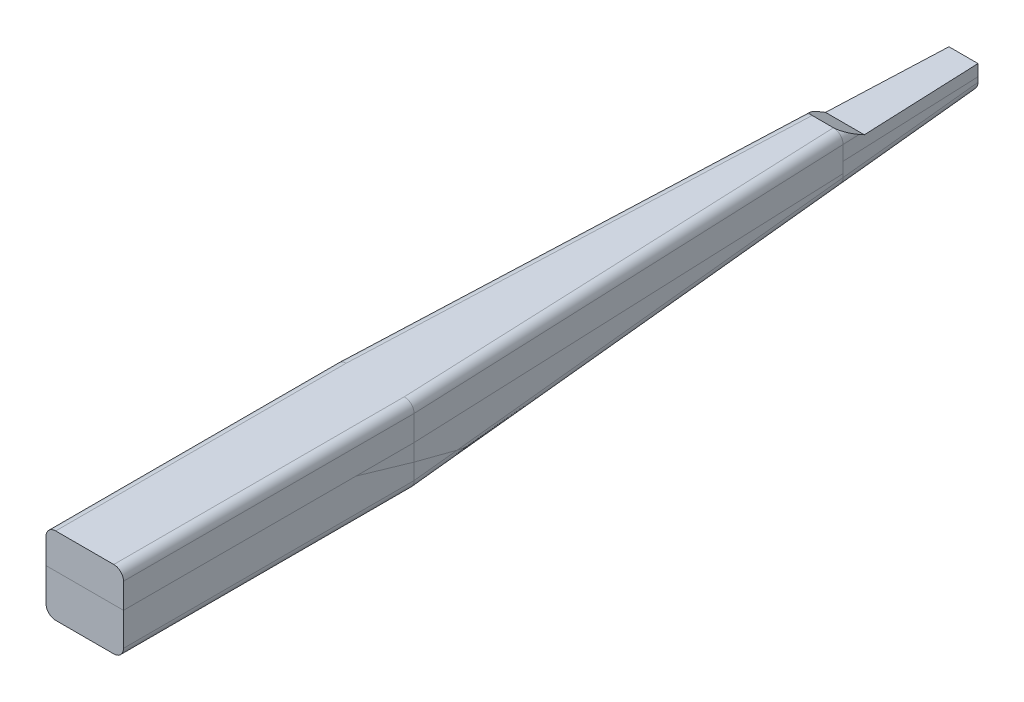
SolidWorks part; units mm, degrees
ref_plane "Front Plane" through (0, 0, 0) normal (0, 0, 1) x (1, 0, 0)
ref_plane "Top Plane" through (0, 0, 0) normal (0, 1, 0) x (1, 0, 0)
ref_plane "Right Plane" through (0, 0, 0) normal (1, 0, 0) x (0, 0, -1)
sketch "Sketch1" plane through (0, 0, 0) normal (0, 0, 1) x (1, 0, 0)
  line L1 (50.8, -50.8) -> (-50.8, -50.8)
  line L2 (50.8, -50.8) -> (50.8, 50.8)
  line L3 (50.8, 50.8) -> (-50.8, 50.8)
  line L4 (-50.8, -50.8) -> (-50.8, 50.8)
  line L5 (50.8, -50.8) -> (-50.8, 50.8) construction
  line L6 (50.8, 50.8) -> (-50.8, -50.8) construction
  point P0 (0, 0)
  dimension "D1" = 101.6
extrude "Boss-Extrude1" add sketch "Sketch1" against normal blind 381.1016
ref_plane "Plane1" through (0, 0, -1152.2456) normal (0, 0, -1) x (-1, 0, 0)
sketch "Sketch2" plane through (0, 0, -1152.2456) normal (0, 0, -1) x (-1, 0, 0)
  line L0 (0, 0) -> (0, 82.164) construction
  line L1 (-50.8, 50.8) -> (50.8, 50.8) construction
  line L2 (-19.05, 50.8) -> (19.05, 50.8)
  line L3 (-19.05, 50.8) -> (-19.05, 0)
  line L4 (-19.05, 0) -> (19.05, 0)
  line L5 (19.05, 50.8) -> (19.05, 0)
  line L6 (-19.05, 50.8) -> (19.05, 0) construction
  line L7 (-19.05, 0) -> (19.05, 50.8) construction
  point P3 (0, 25.4)
  dimension "D1" = 50.8
  dimension "D2" = 38.1
loft "Loft1" add profiles "Sketch2" section "Sketch2" section face at (0, 0, -381.1016) connector at (19.05, 50.8, -1152.2456) connector at (50.8, 50.8, -381.1016)
fillet "Fillet1" radius 12.7 8 edges at (-50.8, -50.8, -190.5508) (-50.8, 50.8, -190.5508) (50.8, 50.8, -190.5508) (50.8, -50.8, -190.5508)
sketch "Sketch3" plane through (50.8, 0, 0) normal (1, 0, 0) x (0, 0, -1)
  line L5 (0, -50.8) -> (0, 5.08)
  line L6 (0, -38.1) -> (0, 38.1) construction
  line L7 (0, 5.08) -> (304.8, 5.08)
  line L8 (304.8, 5.08) -> (475.411, -44.5873)
  line L9 (1152.2456, 0) -> (381.1016, -50.8) construction
  line L10 (475.411, -44.5873) -> (381.1016, -50.8)
  line L11 (381.1016, -50.8) -> (0, -50.8)
  dimension "D1" = 55.88
  dimension "D2" = 304.8
  dimension "D3" = 20
sketch "Sketch4" plane through (0, 0, 0) normal (1, 0, 0) x (0, 0, -1)
  line L0 (1152.2456, 50.8) -> (1152.2456, 34.036)
  line L1 (1152.2456, 38.1) -> (1152.2456, 12.6931) construction
  line L2 (1152.2456, 34.036) -> (996.7976, 34.036)
  line L3 (996.7976, 34.036) -> (967.7615, 50.8)
  line L4 (1152.2456, 50.8) -> (381.1016, 50.8) construction
  line L5 (967.7615, 50.8) -> (1152.2456, 50.8)
  dimension "D1" = 16.764
  dimension "D2" = 155.448
  dimension "D3" = 30
extrude "Cut-Extrude2" cut sketch "Sketch4" against normal mid plane 355.7016
split "Split1" trim tools "Sketch3" bodies to split 104 resulting bodies 105 106
ref_plane "Plane2" through (0, 5.08, 0) normal (0, 1, 0) x (1, 0, 0)
ref_plane "Plane3" through (0, 0, -967.7615) normal (0, 0, 1) x (1, 0, 0)
split "Split3" trim tools "Plane3" bodies to split 105 resulting bodies 109 110
split "Split2" trim tools "Plane2" bodies to split 109 105 resulting bodies 107 108
ref_plane "Plane4" through (0, 19.05, 0) normal (0, 1, 0) x (1, 0, 0)
split "Split4" trim tools "Plane4" bodies to split 110 resulting bodies 111 112
